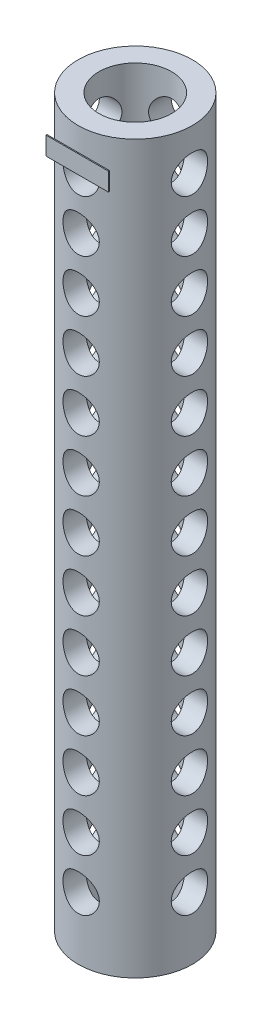
SolidWorks part; units mm, degrees
ref_plane "Front Plane" through (0, 0, 0) normal (0, 0, 1) x (1, 0, 0)
ref_plane "Top Plane" through (0, 0, 0) normal (0, 1, 0) x (1, 0, 0)
ref_plane "Right Plane" through (0, 0, 0) normal (1, 0, 0) x (0, 0, -1)
sketch "Sketch1" plane through (0, 0, 0) normal (0, 1, 0) x (1, 0, 0)
  circle A0 centre (0, 0) radius 5.5
  circle A1 centre (0, 0) radius 3.5
  dimension "D1" = 11
  dimension "D2" = 2
extrude "Boss-Extrude1" add sketch "Sketch1" along normal blind 70
sketch "Sketch2" plane through (0, 0, 0) normal (0, 0, 1) x (1, 0, 0)
  line L0 (0, 70) -> (0, 0) construction
  line L1 (3.5, 70) -> (-3.5, 70) construction
  line L2 (5.5, 70) -> (-5.5, 70) construction
  circle A0 centre (0, 66) radius 1.75
  circle A1 centre (0, 61) radius 1.75
  circle A2 centre (0, 56) radius 1.75
  circle A3 centre (0, 51) radius 1.75
  circle A4 centre (0, 46) radius 1.75
  circle A5 centre (0, 41) radius 1.75
  circle A6 centre (0, 36) radius 1.75
  circle A7 centre (0, 31) radius 1.75
  circle A8 centre (0, 26) radius 1.75
  circle A9 centre (0, 21) radius 1.75
  circle A10 centre (0, 16) radius 1.75
  circle A11 centre (0, 11) radius 1.75
  circle A12 centre (0, 6) radius 1.75
  dimension "D1" = 3.5
  dimension "D2" = 4
  dimension "D3" = 9
  dimension "D4" = 5
extrude "Cut-Extrude1" cut sketch "Sketch2" against normal blind 10 and the other way blind 10
pattern_circular "CirPattern1" count 4 over 360 about axis through (0, 70, 0) along (0, 1, 0) of "Cut-Extrude1"
ref_plane "Plane1" through (0, 0, 5.5) normal (0, 0, 1) x (1, 0, 0)
sketch "Sketch4" plane through (0, 0, 5.5) normal (0, 0, 1) x (1, 0, 0)
  line L0 (0, 66) -> (0, 67.75) construction
  line L1 (3, 66) -> (3, 67.75)
  line L2 (-3, 66) -> (-3, 67.75)
  line L3 (-3, 66) -> (3, 66)
  line L4 (-3, 67.75) -> (3, 67.75)
  circle A0 centre (0, 66) radius 1.75 construction
  dimension "D1" = 3
  dimension "D2" = 3
extrude "Boss-Extrude2" add sketch "Sketch4" along normal blind 0.1 separate body
